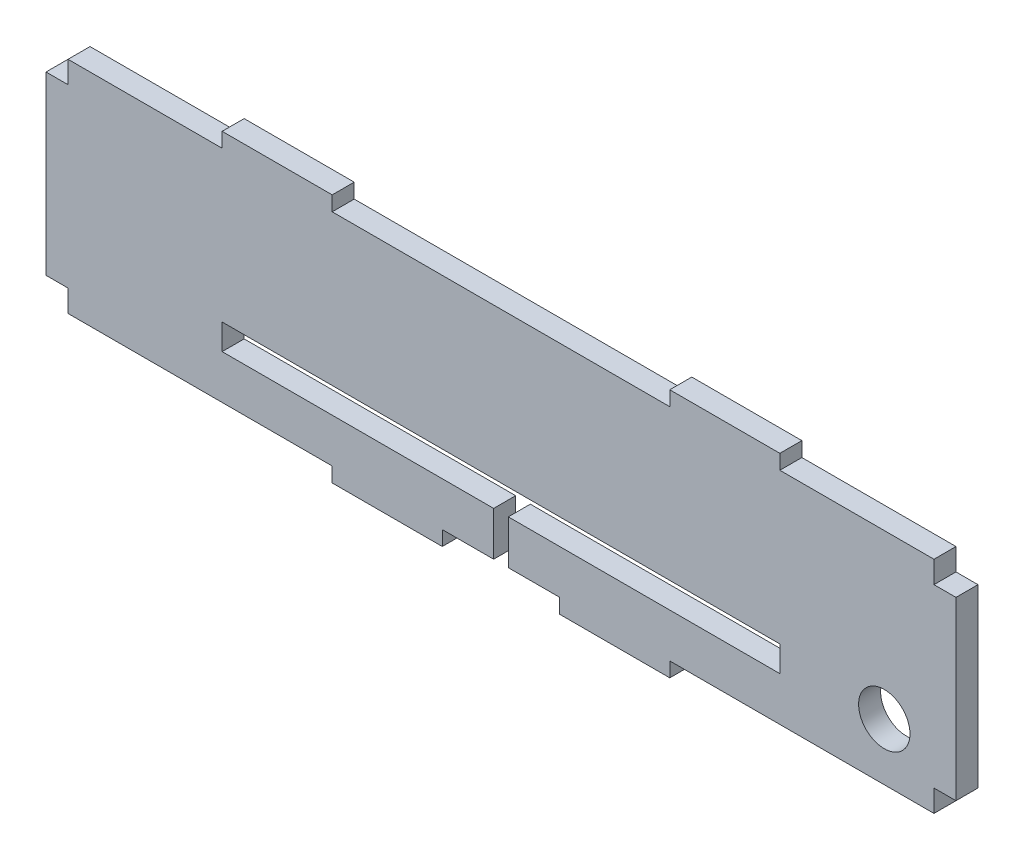
SolidWorks part; units mm, degrees
ref_plane "Front Plane" through (0, 0, 0) normal (0, 0, 1) x (1, 0, 0)
ref_plane "Top Plane" through (0, 0, 0) normal (0, 1, 0) x (1, 0, 0)
ref_plane "Right Plane" through (0, 0, 0) normal (1, 0, 0) x (0, 0, -1)
sketch "Sketch1" plane through (0, 0, 0) normal (0, 0, 1) x (1, 0, 0)
  line L0 (0, 0) -> (0, 43717.3993) construction
  line L1 (-5.9695, 0) -> (43711.4297, 0) construction
  line L2 (3, 0) -> (42, 0)
  line L4 (3, 0) -> (3, 30)
  line L6 (127, 0) -> (127, 30)
  line L7 (42, 0) -> (42, -2)
  line L8 (42, -2) -> (57, -2)
  line L9 (57, -2) -> (57, 0)
  line L10 (57, 0) -> (73, 0)
  line L11 (73, 0) -> (73, -2)
  line L12 (73, -2) -> (88, -2)
  line L13 (88, -2) -> (88, 0)
  line L14 (88, 0) -> (127, 0)
  line L15 (65, 0) -> (65, -50000) construction
  line L16 (27, 9.5) -> (103, 9.5)
  line L17 (27, 9.5) -> (27, 6)
  line L19 (103, 9.5) -> (103, 6)
  line L20 (66, 0) -> (66, 6)
  line L21 (64, 0) -> (66, 0)
  line L22 (64, 0) -> (64, 6)
  line L25 (27, 6) -> (64, 6)
  line L26 (66, 6) -> (103, 6)
  line L27 (3, 30) -> (27, 30)
  line L29 (42, 30) -> (42, 32)
  line L30 (42, 32) -> (27, 32)
  line L31 (27, 30) -> (27, 32)
  line L32 (42, 30) -> (88, 30)
  line L33 (127, 30) -> (103, 30)
  line L34 (103, 30) -> (103, 32)
  line L35 (88, 32) -> (103, 32)
  line L36 (88, 30) -> (88, 32)
  line L37 (127, 3) -> (124, 3)
  line L38 (3, 0) -> (6, 0)
  line L39 (3, 0) -> (3, 3)
  line L40 (3, 3) -> (6, 3)
  line L41 (6, 0) -> (6, 3)
  line L42 (124, 0) -> (124, 3)
  line L43 (127, 0) -> (124, 0)
  line L44 (127, 0) -> (127, 3)
  line L45 (-14.82, 15) -> (49985.18, 15) construction
  line L46 (127, 30) -> (124, 30)
  line L47 (124, 30) -> (124, 27)
  line L48 (127, 27) -> (124, 27)
  line L49 (127, 30) -> (127, 27)
  line L50 (3, 27) -> (6, 27)
  line L51 (6, 30) -> (6, 27)
  line L52 (3, 30) -> (6, 30)
  line L53 (3, 30) -> (3, 27)
  circle A0 centre (117.2288, 7.75) radius 3.5
  point P36 (65, 30)
  dimension "D15" = 7.75
  dimension "D1" = 124
  dimension "D2" = 30
  dimension "D3" = 15
  dimension "D4" = 15
  dimension "D5" = 16
  dimension "D6" = 15
  dimension "D7" = 2
  dimension "D8" = 2
  dimension "D9" = 15
  dimension "D10" = 15
  dimension "D11" = 6
  dimension "D12" = 3.5
  dimension "D13" = 15
  dimension "D14" = 2
  dimension "D16" = 15
  dimension "D17" = 3
  dimension "D18" = 3
  dimension "D19" = 46
extrude "Boss-Extrude3" add sketch "Sketch1" along normal blind 3 contours L36 L32 L29 L30 L31 L27 L4 L2 L7 L8 L9 L10 L22 L25 L17 L16 L19 L26 L20 L11 L12 L13 L14 L6 L33 L34 L35 region at (64.4237, 15.6743, 0)
